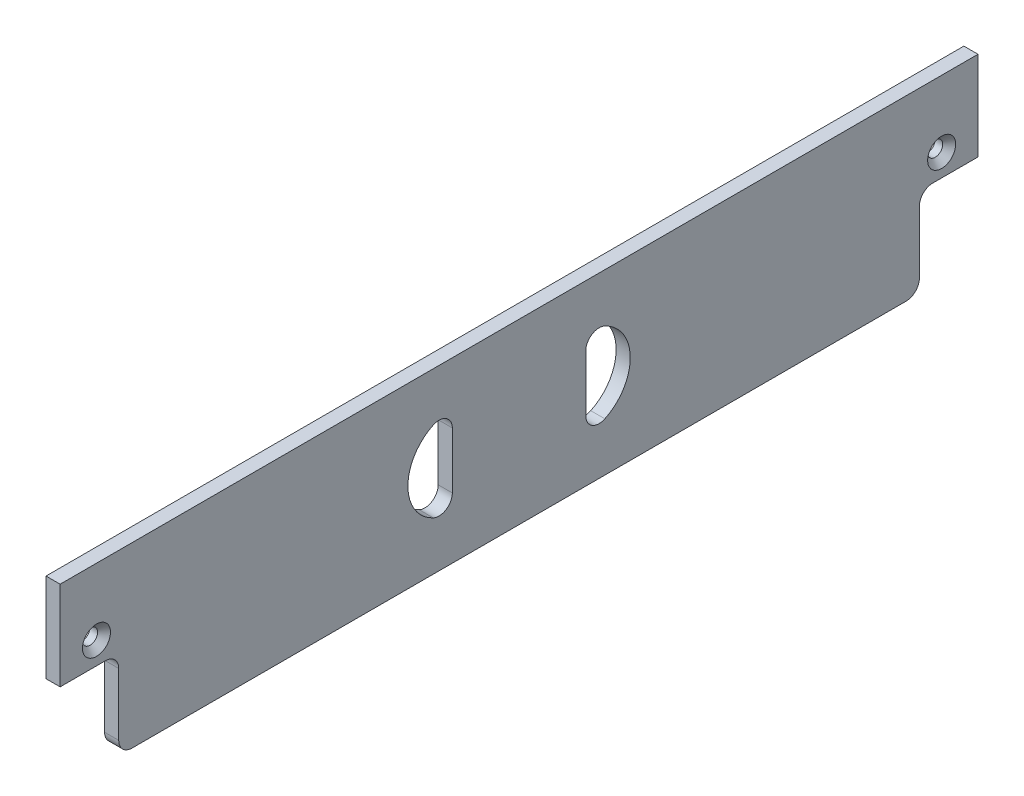
SolidWorks part; units mm, degrees
material "Garolite (G-10/FR4)"
ref_plane "Front Plane" through (0, 0, 0) normal (0, 0, 1) x (1, 0, 0)
ref_plane "Top Plane" through (0, 0, 0) normal (0, 1, 0) x (1, 0, 0)
ref_plane "Right Plane" through (0, 0, 0) normal (1, 0, 0) x (0, 0, -1)
sketch "Sketch1" plane through (0, 0, 0) normal (1, 0, 0) x (0, 0, -1)
  line L0 (-103.175, 20) -> (-103.175, 40)
  line L1 (-103.175, 40) -> (103.175, 40)
  line L2 (0, 0) -> (0, 40) construction
  line L3 (-103.175, 20) -> (-93, 20)
  line L4 (103.175, 20) -> (103.175, 40)
  line L5 (103.175, 20) -> (93, 20)
  line L6 (90, 3) -> (90, 17)
  line L8 (-90, 3) -> (-90, 17)
  line L11 (-87, 0) -> (87, 0)
  arc A0 (-93, 20) -> (-90, 17) centre (-93, 17) cw
  arc A1 (-87, 0) -> (-90, 3) centre (-87, 3) cw
  arc A2 (93, 20) -> (90, 17) centre (93, 17) ccw
  arc A3 (87, 0) -> (90, 3) centre (87, 3) ccw
  dimension "D7" = 3
  dimension "D1" = 40
  dimension "D2" = 206.35
  dimension "D3" = 13.175
  dimension "D4" = 20
extrude "Boss-Extrude1" add sketch "Sketch1" along normal blind 3.175
hole_wizard "CSK for M3 Flat Head Machine Screw1" positions "Sketch3" profile "Sketch2" countersink size "M3" standard "Ansi Metric" end condition through all
sketch "Sketch3" plane through (3.175, 0, 0) normal (1, 0, 0) x (0, 0, -1)
  line L15 (-103.175, 20) -> (-93, 20) construction
  line L16 (-103.175, 40) -> (-103.175, 20) construction
  point P1 (-95, 25)
  dimension "D1" = 5
  dimension "D2" = 8.175
sketch "Sketch2" plane through (3.175, 25, 95) normal (0, 1, 0) x (0, 0, -1)
  line L0 (0, 0) -> (0, 3.175)
  line L1 (0, 3.175) -> (1.7, 3.175)
  line L2 (1.7, 3.175) -> (1.7, 1.45)
  line L3 (1.7, 1.45) -> (3.15, 0)
  line L5 (3.15, 0) -> (0, 0)
  line L6 (-1.7, 1.45) -> (-3.15, 0) construction
  line L11 (0, -6.35) -> (0, 107.95) construction
  dimension "Thru Hole Dia." = 3.4
  dimension "Thru Hole Depth" = 3.175
  dimension "Near C'Sink Dia." = 6.3
  dimension "Near C'Sink Angle" = 90
mirror "Mirror1" about plane through (0, 0, 0) normal (0, 0, 1) of "CSK for M3 Flat Head Machine Screw1"
sketch "Sketch4" plane through (3.175, 0, 0) normal (1, 0, 0) x (0, 0, -1)
  line L0 (-15, 30) -> (-15, 10)
  line L1 (103.175, 40) -> (-103.175, 40) construction
  arc A0 (-15, 30) -> (-15, 10) centre (-15, 20) ccw
  dimension "D1" = 20
  dimension "D2" = 10
  dimension "D3" = 15
extrude "Cut-Extrude1" cut sketch "Sketch4" against normal through all
fillet "Fillet1" radius 3 2 edges at (1.5875, 30, 15) (1.5875, 10, 15)
mirror "Mirror3" about plane through (0, 0, 0) normal (0, 0, 1) of "Cut-Extrude1", "Fillet1"
